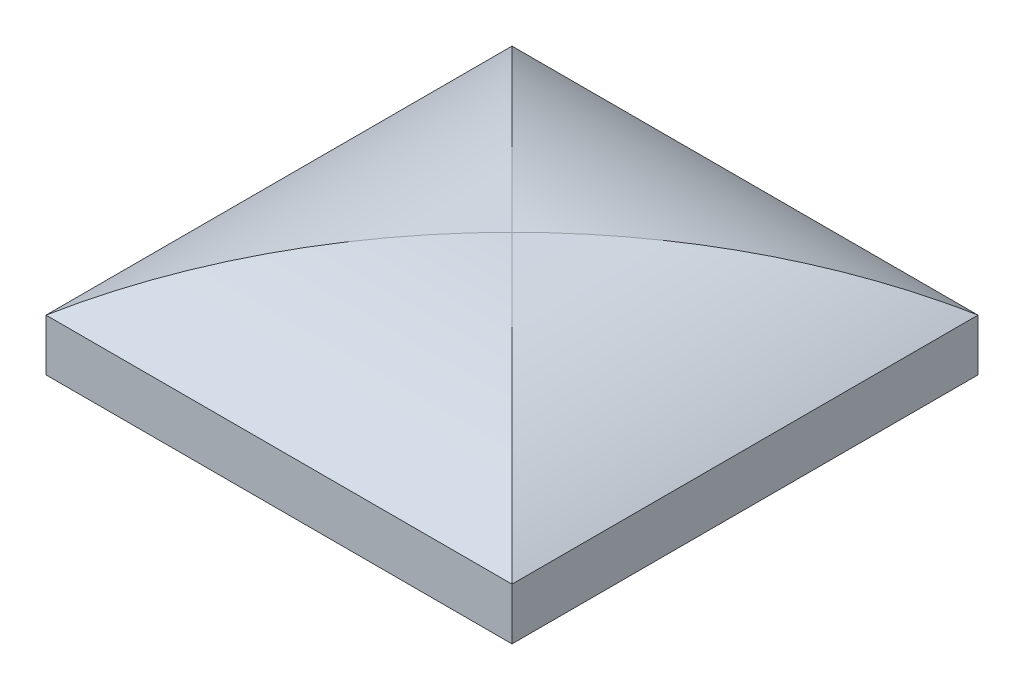
SolidWorks part; units mm, degrees
ref_plane "Спереди" through (0, 0, 0) normal (0, 0, 1) x (1, 0, 0)
ref_plane "Сверху" through (0, 0, 0) normal (0, 1, 0) x (1, 0, 0)
ref_plane "Справа" through (0, 0, 0) normal (1, 0, 0) x (0, 0, -1)
other "Configuration Table"
sketch "Sketch4" plane through (0, 0, 0) normal (0, 0, 1) x (1, 0, 0)
  line L0 (-45, 0) -> (45, 0)
  line L5 (45, 0) -> (45, 10)
  line L6 (-45, 0) -> (-45, 10)
  arc A0 (-45, 10) -> (45, 10) centre (0, -56.1438) cw
  point P4 (0, 0)
  dimension "D3" = 80
  dimension "D1" = 10
  dimension "D2" = 90
extrude "Boss-Extrude6" add sketch "Sketch4" along normal mid plane 90 contours A0 L5 L0 L6
sketch "Sketch9" plane through (0, 0, 0) normal (1, 0, 0) x (0, 0, -1)
  line L0 (-45, 0) -> (45, 0)
  line L1 (45, 0) -> (45, 10)
  line L2 (-45, 0) -> (-45, 10)
  arc A0 (-45, 10) -> (45, 10) centre (0, -56.1438) cw
  point P4 (0, 0)
  dimension "D3" = 80
  dimension "D1" = 10
  dimension "D2" = 90
extrude "Boss-Extrude8" add sketch "Sketch9" along normal mid plane 90 separate body
combine bodies "Combine1" operation type common bodies to combine 110 112
